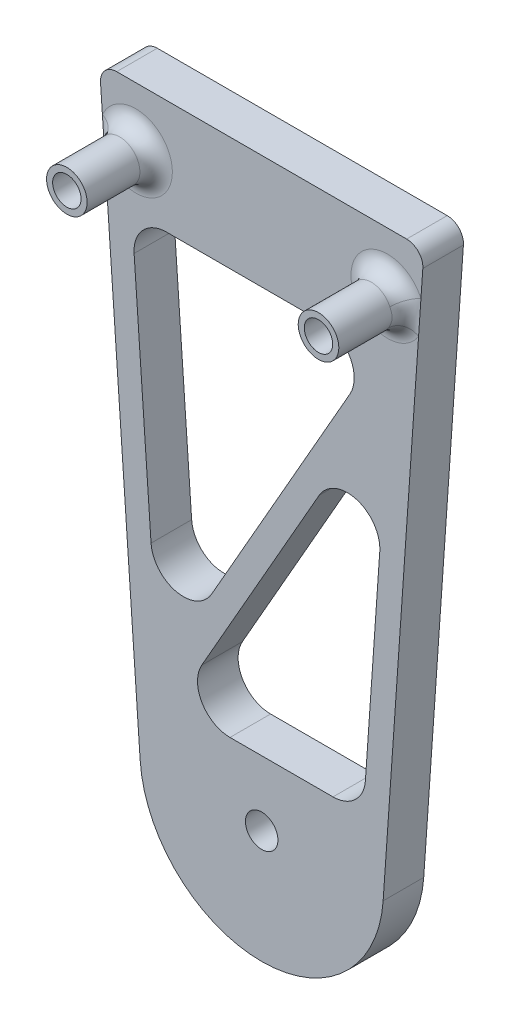
SolidWorks part; units mm, degrees
material "PLA"
ref_plane "Alzado" through (0, 0, 0) normal (0, 0, 1) x (1, 0, 0)
ref_plane "Planta" through (0, 0, 0) normal (0, 1, 0) x (1, 0, 0)
ref_plane "Vista lateral" through (0, 0, 0) normal (1, 0, 0) x (0, 0, -1)
sketch "Croquis1" plane through (0, 0, 0) normal (0, 0, 1) x (1, 0, 0)
  line L0 (0, 0) -> (0, -128.0927) construction
  line L1 (-20.0014, 0) -> (20.0014, 0)
  line L2 (20.0014, 0) -> (14.9635, -72.0463)
  line L3 (-20.0014, 0) -> (-14.9635, -72.0463)
  line L4 (-16.0119, -14.0463) -> (16.0119, -14.0463)
  line L5 (16.0119, -14.0463) -> (12.5155, -64.0463)
  line L6 (12.5155, -64.0463) -> (-12.5155, -64.0463)
  line L7 (-12.5155, -64.0463) -> (-16.0119, -14.0463)
  line L8 (-14.9635, -72.0463) -> (14.9635, -72.0463) construction
  line L9 (-12.7041, -61.35) -> (14.2849, -14.0463)
  line L10 (-12.5155, -64.0463) -> (16.0119, -14.0463) construction
  line L11 (-10.7886, -64.0463) -> (15.7707, -17.496)
  arc A0 (14.9635, -72.0463) -> (-14.9635, -72.0463) centre (0, -71) cw
  circle A1 centre (-15.5, -7.2763) radius 2.5
  circle A2 centre (15.5, -7.2763) radius 2.5
  circle A3 centre (-15.5, -7.2763) radius 1.75
  circle A4 centre (15.5, -7.2763) radius 1.75
  circle A5 centre (0, -72.0463) radius 2
  point P12 (0, -86)
  point P19 (0, -64.0463)
  dimension "D1" = 15
  dimension "D4" = 64.77
  dimension "D5" = 5
  dimension "D7" = 3.5
  dimension "D10" = 4
  dimension "D2" = 86
  dimension "D3" = 86
  dimension "D6" = 31
  dimension "D8" = 3
  dimension "D9" = 50
  dimension "D11" = 8
  dimension "D12" = 3
extrude "Saliente-Extruir1" add sketch "Croquis1" along normal mid plane 5 contours L0 L1 L3 A0 A1 | A1 | A2 | L1 L0 A0 L2 A2 | L6 L11 L5 L4 L9 L7 region at (0, -0.9485, 0) region at (1.6928, -39.1355, 0) region at (-17.9293, -7.2763, 0) region at (13.0707, -7.2763, 0)
extrude "Saliente-Extruir2" add sketch "Croquis1<3>" along normal blind 11 contours A1 | A2 | A3 | A4
sketch "Croquis1<3>" plane through (0, 0, 0) normal (0, 0, 1) x (1, 0, 0) same geometry as "Croquis1"
fillet "Redondeo1" radius 2 2 edges at (18, -7.2763, 2.5) (-13, -7.2763, 2.5)
fillet "Redondeo2" radius 2 2 edges at (20.0014, 0, 0) (-20.0014, 0, 0)
sketch "Croquis2" plane through (0, 0, -2.5) normal (0, 0, -1) x (-1, 0, 0)
  circle A12 centre (-15.5, -7.2763) radius 3
  circle A13 centre (15.5, -7.2763) radius 3
  dimension "D1" = 6
extrude "Cortar-Extruir1" cut sketch "Croquis2" against normal blind 2
fillet "Redondeo3" radius 4 6 edges at (-16.0119, -14.0463, 0) (12.5155, -64.0463, 0) (-10.7886, -64.0463, 0) (-12.7041, -61.35, 0) (14.2849, -14.0463, 0) (15.7707, -17.496, 0)
